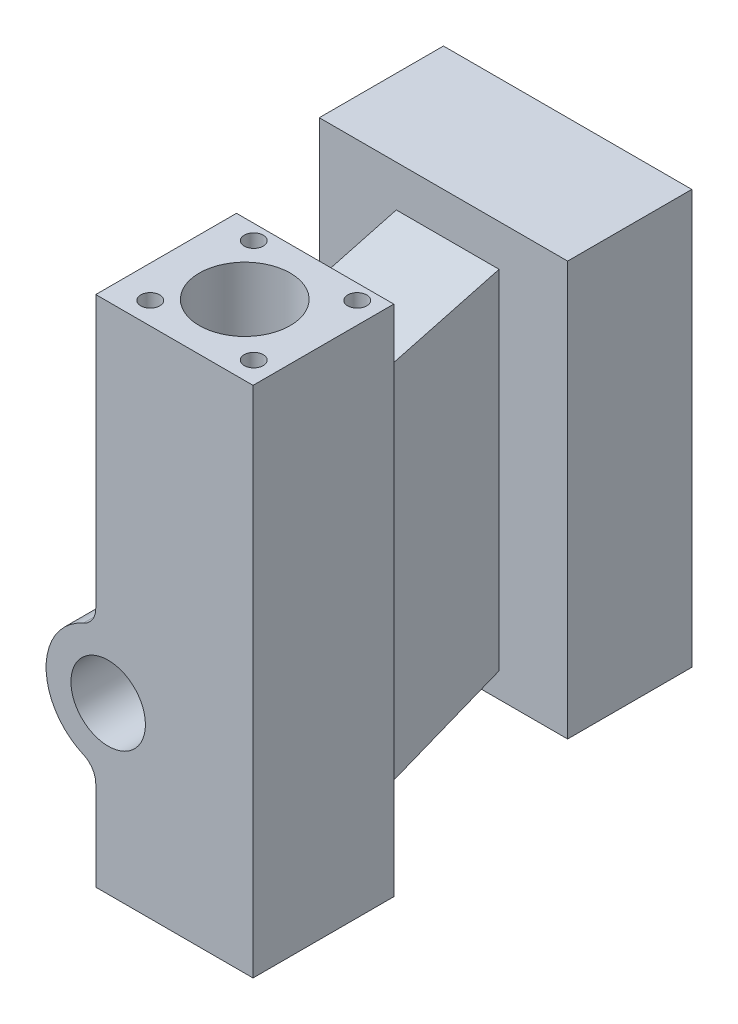
SolidWorks part; units mm, degrees
ref_plane "Front Plane" through (0, 0, 0) normal (0, 0, 1) x (1, 0, 0)
ref_plane "Top Plane" through (0, 0, 0) normal (0, 1, 0) x (1, 0, 0)
ref_plane "Right Plane" through (0, 0, 0) normal (1, 0, 0) x (0, 0, -1)
sketch "Sketch1" plane through (0, 0, 0) normal (0, 0, 1) x (1, 0, 0)
  line L1 (-26.1812, 49.3094) -> (11.8188, 49.3094)
  line L2 (-26.1812, 49.3094) -> (-26.1812, -74.6906)
  line L3 (-26.1812, -74.6906) -> (11.8188, -74.6906)
  line L4 (11.8188, 49.3094) -> (11.8188, -74.6906)
  dimension "D1" = 124
  dimension "D2" = 38
extrude "Boss-Extrude1" add sketch "Sketch1" along normal blind 34
sketch "Sketch2" plane through (0, 0, 34) normal (0, 0, 1) x (1, 0, 0)
  line L4 (11.8188, -74.6906) -> (11.8188, 49.3094) construction
  line L5 (-26.1812, -74.6906) -> (11.8188, -74.6906) construction
  circle A0 centre (-23.1812, -34.6906) radius 15
  point P8 (0, 0)
  dimension "D1" = 35
  dimension "D2" = 40
extrude "Boss-Extrude2" add sketch "Sketch2" against normal blind 34
fillet "Fillet1" radius 5 2 edges at (-26.1812, -49.3876, 17) (-26.1812, -19.9937, 17)
sketch "Sketch3" plane through (0, -74.6906, 0) normal (0, -1, 0) x (1, 0, 0)
  line L0 (11.8188, 34) -> (11.8188, 0) construction
  line L1 (-26.1812, 34) -> (11.8188, 34) construction
  circle A0 centre (-7.1812, 17) radius 11
  dimension "D1" = 19
  dimension "D2" = 17
extrude "Cut-Extrude1" cut sketch "Sketch3" against normal blind 1000
sketch "Sketch4" plane through (0, 0, 34) normal (0, 0, 1) x (1, 0, 0)
  circle A0 centre (-23.1812, -34.6906) radius 9
  arc A1 (-29.1812, -20.9429) -> (-29.1812, -48.4384) centre (-23.1812, -34.6906) ccw construction
  dimension "D1" = 18
sketch "Sketch5" plane through (0, 0, 0) normal (0, 0, -1) x (-1, 0, 0)
  line L1 (-7.2618, 48.6909) -> (17.5691, 48.6909)
  line L2 (-7.2618, 48.6909) -> (-7.2618, -62.513)
  line L3 (-7.2618, -62.513) -> (17.5691, -62.513)
  line L4 (17.5691, 48.6909) -> (17.5691, -62.513)
extrude "Boss-Extrude3" add sketch "Sketch5" along normal blind 30
sketch "Sketch6" plane through (0, 0, -30) normal (0, 0, -1) x (-1, 0, 0)
  line L0 (26.1812, 49.3094) -> (26.1812, -16.3603) construction
  line L1 (-23.8188, 49.3094) -> (36.1812, 49.3094)
  line L2 (-23.8188, 49.3094) -> (-23.8187, -50.6906)
  line L3 (-23.8187, -50.6906) -> (36.1812, -50.6906)
  line L4 (36.1812, 49.3094) -> (36.1812, -50.6906)
  line L5 (-11.8188, 49.3094) -> (26.1812, 49.3094) construction
  dimension "D1" = 60
  dimension "D2" = 100
  dimension "D3" = 10
extrude "Boss-Extrude4" add sketch "Sketch6" along normal blind 30
sketch "Sketch9" plane through (7.2618, 0, 0) normal (1, 0, 0) x (0, 0, -1)
  line L0 (0, 52.6027) -> (0, 31.3094)
  line L1 (0, 31.3094) -> (30, 39.3094)
  line L2 (30, 39.3094) -> (30, 52.6027)
  line L3 (30, 52.6027) -> (0, 52.6027)
  line L4 (0, -56.6906) -> (0, -66.3738)
  line L5 (0, -66.3738) -> (30, -69.2814)
  line L6 (30, -69.2814) -> (30, -44.6906)
  line L7 (30, -44.6906) -> (0, -56.6906)
  line L8 (30, -50.6906) -> (30, 48.6909) construction
  line L9 (0, 49.3094) -> (0, -16.3603) construction
  line L10 (30, -50.6906) -> (30, 49.3094) construction
  line L11 (60, 49.3094) -> (30, 49.3094) construction
  line L12 (-34, 49.3094) -> (0, 49.3094) construction
  line L13 (60, -50.6906) -> (30, -50.6906) construction
  line L14 (-34, -74.6906) -> (0, -74.6906) construction
  dimension "D1" = 10
  dimension "D2" = 18
  dimension "D3" = 6
  dimension "D4" = 18
extrude "Cut-Extrude5" cut sketch "Sketch9" against normal blind 100
sketch "Sketch10" plane through (-36.1812, 0, 0) normal (-1, 0, 0) x (0, 0, 1)
  line L0 (-60, -50.6906) -> (-60, 49.3094) construction
  line L1 (-60, -50.6906) -> (-30, -50.6906) construction
  circle A0 centre (-45, -15.6906) radius 7.5
  dimension "D3" = 15
  dimension "D1" = 15
  dimension "D2" = 35
extrude "Cut-Extrude6" cut sketch "Sketch10" against normal blind 10
sketch "Sketch11" plane through (0, 49.3094, 0) normal (0, 1, 0) x (1, 0, 0)
  circle A0 centre (6.6247, -28.639) radius 2.3015
extrude "Cut-Extrude7" cut sketch "Sketch11" against normal blind 10
pattern_linear "LPattern1" count 2 spacing 25 along (-1, 0, 0) count 2 spacing 25 along (0, 0, -1) of "Cut-Extrude7"
extrude "Вырез-Вытянуть1" cut sketch "Sketch4" against normal blind 17
